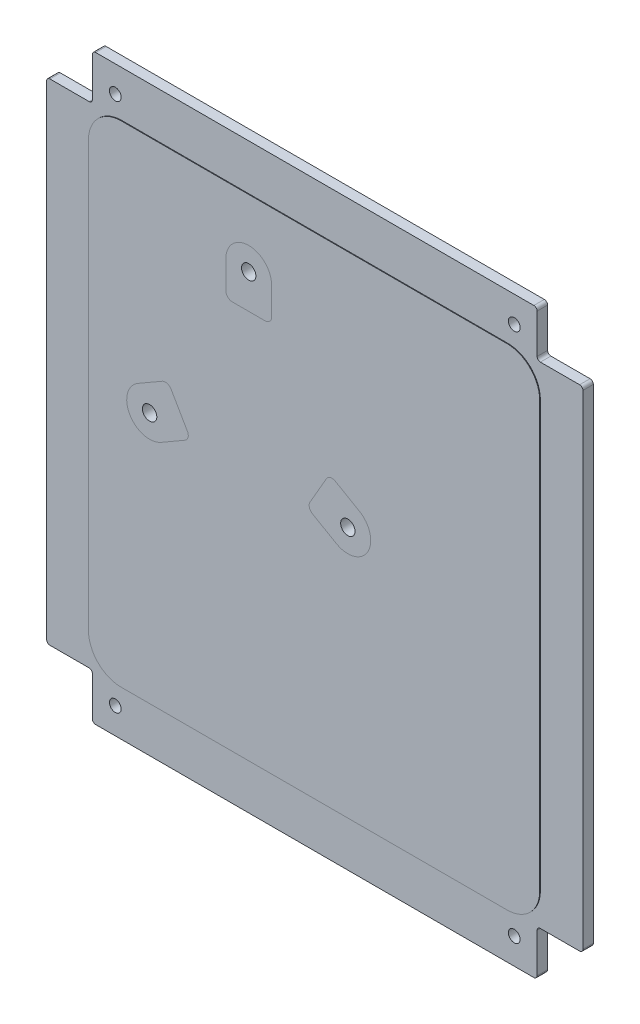
SolidWorks part; units mm, degrees
material "PET"
ref_plane "Front Plane" through (0, 0, 0) normal (0, 0, 1) x (1, 0, 0)
ref_plane "Top Plane" through (0, 0, 0) normal (0, 1, 0) x (1, 0, 0)
ref_plane "Right Plane" through (0, 0, 0) normal (1, 0, 0) x (0, 0, -1)
sketch "Sketch1" plane through (0, 0, 0) normal (0, 0, 1) x (1, 0, 0)
  line L0 (-34, 44) -> (-34, 38)
  line L1 (-33.5, -44.5) -> (33.5, -44.5)
  line L2 (-41, 37) -> (-41, -37)
  line L3 (-33.5, 44.5) -> (33.5, 44.5)
  line L4 (41, -37) -> (41, 37)
  line L5 (34, -44) -> (34, -38)
  line L6 (34.5, -37.5) -> (40.5, -37.5)
  line L7 (-34.5, 37.5) -> (-40.5, 37.5)
  line L8 (34, 44) -> (34, 38)
  line L9 (34.5, 37.5) -> (40.5, 37.5)
  line L10 (-40.5, -37.5) -> (-34.5, -37.5)
  line L11 (-34, -38) -> (-34, -44)
  line L12 (-34.5, -38) -> (34.5, 38) construction
  line L13 (34.5, -38) -> (-34.5, 38) construction
  arc A0 (-33.5, 44.5) -> (-34, 44) centre (-33.5, 44) ccw
  arc A1 (33.5, 44.5) -> (34, 44) centre (33.5, 44) cw
  arc A2 (34, 38) -> (34.5, 37.5) centre (34.5, 38) ccw
  arc A3 (40.5, 37.5) -> (41, 37) centre (40.5, 37) cw
  arc A4 (33.5, -44.5) -> (34, -44) centre (33.5, -44) ccw
  arc A5 (34.5, -37.5) -> (34, -38) centre (34.5, -38) ccw
  arc A6 (40.5, -37.5) -> (41, -37) centre (40.5, -37) ccw
  arc A7 (-34, -44) -> (-33.5, -44.5) centre (-33.5, -44) ccw
  arc A8 (-34, -38) -> (-34.5, -37.5) centre (-34.5, -38) ccw
  arc A9 (-41, -37) -> (-40.5, -37.5) centre (-40.5, -37) ccw
  arc A10 (-40.5, 37.5) -> (-41, 37) centre (-40.5, 37) ccw
  arc A11 (-34.5, 37.5) -> (-34, 38) centre (-34.5, 38) ccw
  point P0 (0, 0)
  dimension "D4" = 0.5
  dimension "D1" = 7
  dimension "D2" = 7
  dimension "D3" = 7
  dimension "D5" = 7
  dimension "D6" = 7
  dimension "D7" = 7
  dimension "D8" = 7
  dimension "D9" = 7
  dimension "D10" = 89
  dimension "D11" = 82
extrude "Boss-Extrude1" add sketch "Sketch1" along normal blind 1.6
sketch "Esboço1" plane through (0, 0, 1.6) normal (0, 0, 1) x (1, 0, 0)
  line L1 (-29.5, -37.5) -> (29.5, -37.5)
  line L2 (-34.5, -32.5) -> (-34.5, 32.5)
  line L3 (-29.5, 37.5) -> (29.5, 37.5)
  line L4 (34.5, -32.5) -> (34.5, 32.5)
  line L5 (-29.5, -32.5) -> (29.5, 32.5) construction
  line L6 (-29.5, 32.5) -> (29.5, -32.5) construction
  arc A0 (-34.5, 32.5) -> (-29.5, 37.5) centre (-29.5, 32.5) cw
  arc A1 (29.5, 37.5) -> (34.5, 32.5) centre (29.5, 32.5) cw
  arc A2 (34.5, -32.5) -> (29.5, -37.5) centre (29.5, -32.5) cw
  arc A3 (-29.5, -37.5) -> (-34.5, -32.5) centre (-29.5, -32.5) cw
  point P0 (0, 0)
  dimension "D1" = 5
  dimension "D2" = 69
  dimension "D3" = 75
extrude "Boss-Extrude2" add sketch "Esboço1" along normal blind 0.1
hole_wizard "M1.6 Hole1-FixingStructure" positions "Sketch3" profile "Sketch2" hole size "M1.6" standard "DIN"
sketch "Sketch3" plane through (0, 0, 0) normal (0, 0, -1) x (-1, 0, 0)
  line L0 (-33.5, 44.5) -> (33.5, 44.5) construction
  line L1 (33.5, -44.5) -> (-33.5, -44.5) construction
  line L2 (-41, -37) -> (-41, 37) construction
  line L3 (41, 37) -> (41, -37) construction
  point P0 (-30.5, 40.5)
  point P2 (30.5, 40.5)
  point P4 (-30.5, -40.5)
  point P6 (30.5, -40.5)
  dimension "D1" = 4
  dimension "D2" = 4
  dimension "D3" = 10.5
  dimension "D4" = 10.5
sketch "Sketch2" plane through (30.5, 40.5, 0) normal (1, 0, 0) x (0, 1, 0)
  line L0 (0, 0) -> (0, 200.5408)
  line L1 (0, 200.5408) -> (0.9, 200)
  line L2 (0.9, 200) -> (0.9, 0)
  line L5 (0.9, 0) -> (0, 0)
  line L10 (0, 200.5408) -> (-0.9, 200) construction
  line L11 (0, -6.35) -> (0, 107.95) construction
  dimension "Hole Dia." = 1.8
  dimension "Hole Depth" = 200
  dimension "Drill Angle" = 118
sketch "Sketch4" plane through (0, 0, 1.7) normal (0, 0, 1) x (1, 0, 0)
  circle A0 centre (-25.1554, 1) radius 1.1 construction
  circle A1 centre (-10, 27.25) radius 1.1 construction
  circle A2 centre (5.1554, 1) radius 1.1 construction
  circle A3 centre (-25.1554, 1) radius 1.1
  circle A4 centre (-10, 27.25) radius 1.1
  circle A5 centre (5.1554, 1) radius 1.1
extrude "Cut-Extrude1" cut sketch "Sketch4" against normal up to surface (1.7 mm away) up to face at (29.6, 40.5, 0)
sketch "Sketch5" plane through (0, 0, 1.7) normal (0, 0, 1) x (1, 0, 0)
  line L4 (-20.2391, 0.9517) -> (-22.7391, 5.2818) construction
  line L5 (-19.3731, 1.4517) -> (-21.8731, 5.7818)
  line L6 (-20.1795, -0.1686) -> (-23.4054, -2.0311)
  line L7 (-26.9054, 4.0311) -> (-23.6795, 5.8936)
  line L8 (-19.7391, 0.0857) -> (-23.4054, -2.0311)
  line L9 (-26.9054, 4.0311) -> (-23.2391, 6.1478)
  line L10 (-19.3731, 1.4517) -> (-21.8731, 5.7818) construction
  line L11 (-12.5, 22.0165) -> (-7.5, 22.0165)
  line L12 (-13.5, 23.0165) -> (-13.5, 27.25)
  line L13 (-6.5, 27.25) -> (-6.5, 23.0165)
  line L14 (-12.5, 23.0165) -> (-7.5, 23.0165) construction
  line L15 (1.8731, 5.7818) -> (-0.6269, 1.4517)
  line L16 (3.2391, 6.1478) -> (6.9054, 4.0311)
  line L17 (3.4054, -2.0311) -> (-0.2609, 0.0857)
  line L18 (2.7391, 5.2818) -> (0.2391, 0.9517) construction
  circle A0 centre (-10, 9.75) radius 10 construction
  arc A3 (-23.2391, 6.1478) -> (-21.8731, 5.7818) centre (-22.7391, 5.2818) cw
  arc A4 (-26.9054, 4.0311) -> (-23.4054, -2.0311) centre (-25.1554, 1) ccw
  arc A5 (-26.9054, 4.0311) -> (-23.4054, -2.0311) centre (-25.1554, 1) ccw
  arc A6 (-19.3731, 1.4517) -> (-19.7391, 0.0857) centre (-20.2391, 0.9517) cw
  arc A7 (-6.5, 23.0165) -> (-7.5, 22.0165) centre (-7.5, 23.0165) cw
  arc A8 (-6.5, 27.25) -> (-13.5, 27.25) centre (-10, 27.25) ccw
  arc A9 (-12.5, 22.0165) -> (-13.5, 23.0165) centre (-12.5, 23.0165) cw
  arc A10 (-0.2609, 0.0857) -> (-0.6269, 1.4517) centre (0.2391, 0.9517) cw
  arc A11 (3.4054, -2.0311) -> (6.9054, 4.0311) centre (5.1554, 1) ccw
  arc A12 (1.8731, 5.7818) -> (3.2391, 6.1478) centre (2.7391, 5.2818) cw
  point P0 (-10, 9.75)
  point P44 (-10, 9.75)
  dimension "D3" = 1
  dimension "D1" = 1
  dimension "D2" = 1
  dimension "D4" = 3
split line "Split Line1"
